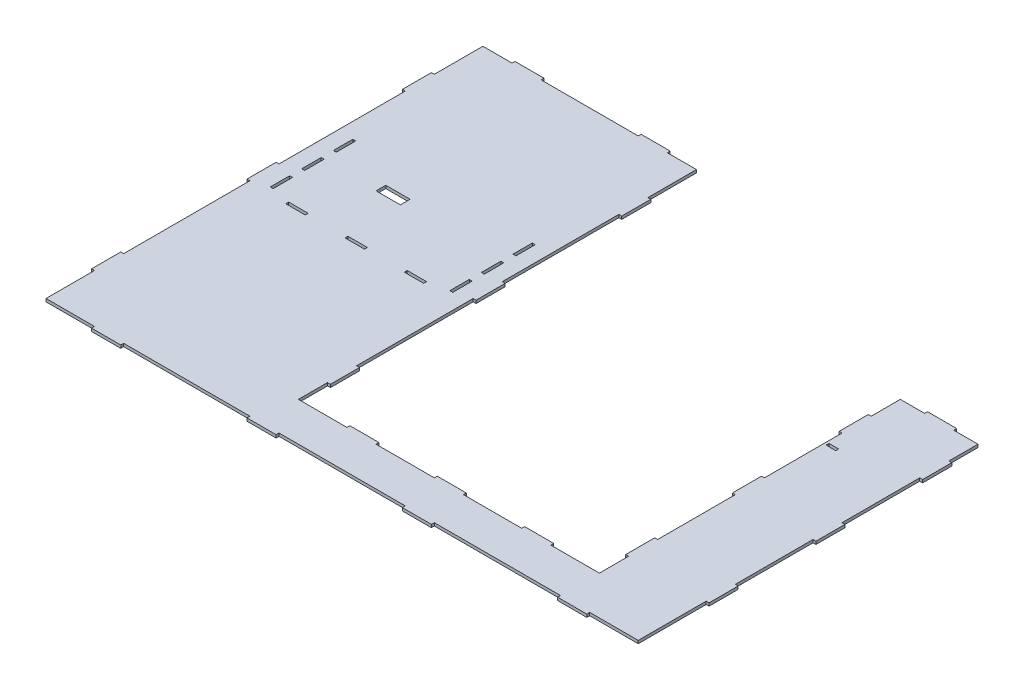
SolidWorks part; units mm, degrees
material "ABS"
ref_plane "Front Plane" through (0, 0, 0) normal (0, 0, 1) x (1, 0, 0)
ref_plane "Top Plane" through (0, 0, 0) normal (0, 1, 0) x (1, 0, 0)
ref_plane "Right Plane" through (0, 0, 0) normal (1, 0, 0) x (0, 0, -1)
sketch "Sketch1" plane through (0, 0, 0) normal (0, 1, 0) x (1, 0, 0)
  line L0 (0, 0) -> (0, 50)
  line L1 (0, 450) -> (30, 450)
  line L2 (220, 450) -> (220, 400)
  line L3 (220, 40) -> (270, 40)
  line L5 (610, 0) -> (560, 0)
  line L6 (530, 40) -> (530, 70)
  line L7 (530, 350) -> (555, 350)
  line L8 (610, 0) -> (610, 70)
  line L9 (220, 70) -> (220, 40)
  line L10 (-3, 400) -> (0, 400)
  line L11 (-3, 400) -> (-3, 370)
  line L12 (-3, 370) -> (0, 370)
  line L14 (-3, 240) -> (0, 240)
  line L15 (-3, 240) -> (-3, 210)
  line L16 (-3, 210) -> (0, 210)
  line L18 (-3, 80) -> (0, 80)
  line L19 (-3, 80) -> (-3, 50)
  line L20 (-3, 50) -> (0, 50)
  line L34 (220, 400) -> (223, 400)
  line L36 (220, 370) -> (223, 370)
  line L37 (223, 400) -> (223, 370)
  line L38 (220, 250) -> (223, 250)
  line L40 (220, 220) -> (223, 220)
  line L41 (223, 250) -> (223, 220)
  line L42 (220, 100) -> (223, 100)
  line L44 (220, 70) -> (223, 70)
  line L45 (223, 100) -> (223, 70)
  line L46 (610, 320) -> (613, 320)
  line L48 (610, 290) -> (613, 290)
  line L49 (613, 320) -> (613, 290)
  line L50 (610, 210) -> (613, 210)
  line L52 (610, 180) -> (613, 180)
  line L53 (613, 210) -> (613, 180)
  line L58 (610, 100) -> (613, 100)
  line L60 (610, 70) -> (613, 70)
  line L61 (613, 100) -> (613, 70)
  line L62 (530, 320) -> (527, 320)
  line L64 (530, 290) -> (527, 290)
  line L65 (527, 320) -> (527, 290)
  line L66 (530, 210) -> (527, 210)
  line L68 (530, 180) -> (527, 180)
  line L69 (527, 210) -> (527, 180)
  line L70 (530, 100) -> (527, 100)
  line L72 (530, 70) -> (527, 70)
  line L73 (527, 100) -> (527, 70)
  line L74 (220, 220) -> (220, 100)
  line L75 (220, 370) -> (220, 250)
  line L76 (530, 100) -> (530, 180)
  line L77 (530, 210) -> (530, 290)
  line L78 (530, 320) -> (530, 350)
  line L79 (610, 320) -> (610, 350)
  line L80 (610, 210) -> (610, 290)
  line L81 (610, 100) -> (610, 180)
  line L82 (0, 80) -> (0, 210)
  line L83 (0, 240) -> (0, 370)
  line L84 (0, 400) -> (0, 450)
  line L85 (190, 450) -> (220, 450)
  line L87 (30, 450) -> (30, 453)
  line L88 (30, 453) -> (60, 453)
  line L89 (60, 450) -> (60, 453)
  line L91 (160, 450) -> (160, 453)
  line L92 (160, 453) -> (190, 453)
  line L93 (190, 450) -> (190, 453)
  line L94 (60, 450) -> (160, 450)
  line L95 (585, 350) -> (610, 350)
  line L97 (555, 350) -> (555, 353)
  line L98 (555, 353) -> (585, 353)
  line L99 (585, 350) -> (585, 353)
  line L100 (300, 40) -> (360, 40)
  line L102 (270, 40) -> (270, 43)
  line L103 (270, 43) -> (300, 43)
  line L104 (300, 40) -> (300, 43)
  line L106 (450, 40) -> (450, 43)
  line L107 (450, 43) -> (480, 43)
  line L108 (480, 40) -> (480, 43)
  line L110 (360, 40) -> (360, 43)
  line L111 (360, 43) -> (390, 43)
  line L112 (390, 40) -> (390, 43)
  line L113 (390, 40) -> (450, 40)
  line L114 (480, 40) -> (530, 40)
  line L115 (50, 0) -> (0, 0)
  line L117 (50, 0) -> (50, -3)
  line L118 (50, -3) -> (80, -3)
  line L119 (80, 0) -> (80, -3)
  line L121 (370, 0) -> (370, -3)
  line L122 (370, -3) -> (400, -3)
  line L123 (400, 0) -> (400, -3)
  line L125 (530, 0) -> (530, -3)
  line L126 (530, -3) -> (560, -3)
  line L127 (560, 0) -> (560, -3)
  line L129 (210, 0) -> (210, -3)
  line L130 (210, -3) -> (240, -3)
  line L131 (240, 0) -> (240, -3)
  line L132 (210, 0) -> (80, 0)
  line L133 (370, 0) -> (240, 0)
  line L134 (530, 0) -> (400, 0)
  line L135 (110, 450) -> (110, 320) construction
  line L136 (16, 235) -> (19, 235)
  line L137 (16, 235) -> (16, 215)
  line L138 (16, 215) -> (19, 215)
  line L139 (19, 235) -> (19, 215)
  line L140 (16, 267.5) -> (19, 267.5)
  line L141 (16, 267.5) -> (16, 247.5)
  line L142 (16, 247.5) -> (19, 247.5)
  line L143 (19, 267.5) -> (19, 247.5)
  line L144 (16, 300) -> (19, 300)
  line L145 (16, 300) -> (16, 280)
  line L146 (16, 280) -> (19, 280)
  line L147 (19, 300) -> (19, 280)
  line L148 (39, 211) -> (59, 211)
  line L149 (39, 211) -> (39, 208)
  line L150 (39, 208) -> (59, 208)
  line L151 (59, 211) -> (59, 208)
  line L152 (100, 211) -> (120, 211)
  line L153 (100, 211) -> (100, 208)
  line L154 (100, 208) -> (120, 208)
  line L155 (120, 211) -> (120, 208)
  line L156 (161, 211) -> (181, 211)
  line L157 (161, 211) -> (161, 208)
  line L158 (161, 208) -> (181, 208)
  line L159 (181, 211) -> (181, 208)
  line L160 (204, 215) -> (201, 215)
  line L161 (201, 235) -> (201, 215)
  line L162 (204, 235) -> (204, 215)
  line L163 (204, 235) -> (201, 235)
  line L164 (204, 247.5) -> (201, 247.5)
  line L165 (201, 267.5) -> (201, 247.5)
  line L166 (204, 267.5) -> (204, 247.5)
  line L167 (204, 267.5) -> (201, 267.5)
  line L168 (204, 280) -> (201, 280)
  line L169 (201, 300) -> (201, 280)
  line L170 (204, 300) -> (201, 300)
  line L171 (204, 300) -> (204, 280)
  dimension "D1" = 220
  dimension "D2" = 610
  dimension "D3" = 450
  dimension "D4" = 350
  dimension "D5" = 80
  dimension "D6" = 40
  dimension "D7" = 30
  dimension "D8" = 3
  dimension "D9" = 30
  dimension "D10" = 50
  dimension "D11" = 3
  dimension "D12" = 30
  dimension "D13" = 30
  dimension "D14" = 130
  dimension "D15" = 30
  dimension "D16" = 3
  dimension "D17" = 3
  dimension "D18" = 50
  dimension "D19" = 3
  dimension "D20" = 30
  dimension "D21" = 30
  dimension "D22" = 3
  dimension "D23" = 50
  dimension "D24" = 120
  dimension "D25" = 120
  dimension "D26" = 30
  dimension "D27" = 3
  dimension "D28" = 30
  dimension "D29" = 3
  dimension "D30" = 3
  dimension "D31" = 30
  dimension "D32" = 30
  dimension "D33" = 3
  dimension "D34" = 80
  dimension "D35" = 3
  dimension "D36" = 30
  dimension "D37" = 3
  dimension "D38" = 3
  dimension "D39" = 80
  dimension "D40" = 3
  dimension "D41" = 30
  dimension "D42" = 30
  dimension "D43" = 30
  dimension "D44" = 3
  dimension "D45" = 80
  dimension "D46" = 3
  dimension "D47" = 30
  dimension "D48" = 80
  dimension "D49" = 30
  dimension "D50" = 30
  dimension "D51" = 30
  dimension "D52" = 3
  dimension "D53" = 25
  dimension "D54" = 30
  dimension "D55" = 30
  dimension "D56" = 30
  dimension "D57" = 3
  dimension "D58" = 3
  dimension "D59" = 3
  dimension "D60" = 50
  dimension "D61" = 50
  dimension "D62" = 60
  dimension "D63" = 3
  dimension "D64" = 30
  dimension "D65" = 30
  dimension "D66" = 30
  dimension "D67" = 30
  dimension "D68" = 3
  dimension "D69" = 3
  dimension "D70" = 3
  dimension "D71" = 50
  dimension "D72" = 50
  dimension "D73" = 130
  dimension "D74" = 130
  dimension "D75" = 20
  dimension "D76" = 215
  dimension "D77" = 3
  dimension "D78" = 16
  dimension "D79" = 12.5
  dimension "D80" = 3
  dimension "D81" = 20
  dimension "D82" = 16
  dimension "D83" = 3
  dimension "D84" = 20
  dimension "D85" = 12.5
  dimension "D86" = 16
  dimension "D87" = 20
  dimension "D88" = 20
  dimension "D89" = 20
  dimension "D90" = 3
  dimension "D91" = 3
  dimension "D92" = 20
  dimension "D93" = 3
  dimension "D94" = 4
  dimension "D95" = 4
  dimension "D96" = 41
  dimension "D97" = 4
  dimension "D98" = 41
extrude "Boss-Extrude1" add sketch "Sketch1" along normal blind 3 contours L133 L131 L130 L129 L132 L119 L118 L117 L115 L0 L20 L19 L18 L82 L16 L15 L14 L83 L12 L11 L10 L84 L1 L87 L88 L89 L94 L91 L92 L93 L85 L2 L34 L37 L36 L75 L38 L41 L40 L74 L42 L45 L44 L9 L3 L102 L103 L104 L100 L110 L111 L112 L113 L106 L107 L108 L114 L6 L72 L73 L70 L76 L68 L69 L66 L77 L64 L65 L62 L78 L7 L97 L98 L99 L95 L79 L46 L49 L48 L80 L50 L53 L52 L81 L58 L61 L60 L8 L5 L127 L126 L125 L134 L123 L122 L121 | L147 L146 L145 L144 | L141 L142 L143 L140 | L139 L138 L137 L136 | L148 L151 L150 L149 | L152 L155 L154 L153 | L156 L159 L158 L157 | L161 L160 L162 L163 | L166 L164 L165 L167 | L169 L168 L171 L170
sketch "Sketch2" plane through (0, 3, 0) normal (0, 1, 0) x (1, 0, 0)
  line L0 (530, 210) -> (530, 290) construction
  line L1 (532.5, 274) -> (542.5, 274)
  line L2 (532.5, 274) -> (532.5, 271)
  line L3 (532.5, 271) -> (542.5, 271)
  line L4 (542.5, 274) -> (542.5, 271)
  line L5 (530, 350) -> (555, 350) construction
  line L6 (19, 235) -> (19, 215) construction
  line L7 (74, 276) -> (99, 276)
  line L8 (74, 276) -> (74, 266)
  line L9 (74, 266) -> (99, 266)
  line L10 (99, 276) -> (99, 266)
  line L11 (39, 211) -> (59, 211) construction
  point P14 (19, 225)
  dimension "D1" = 10
  dimension "D2" = 3
  dimension "D3" = 2.5
  dimension "D4" = 76
  dimension "D5" = 25
  dimension "D6" = 10
  dimension "D7" = 55
  dimension "D8" = 55
extrude "Cut-Extrude1" cut sketch "Sketch2" against normal blind 10
